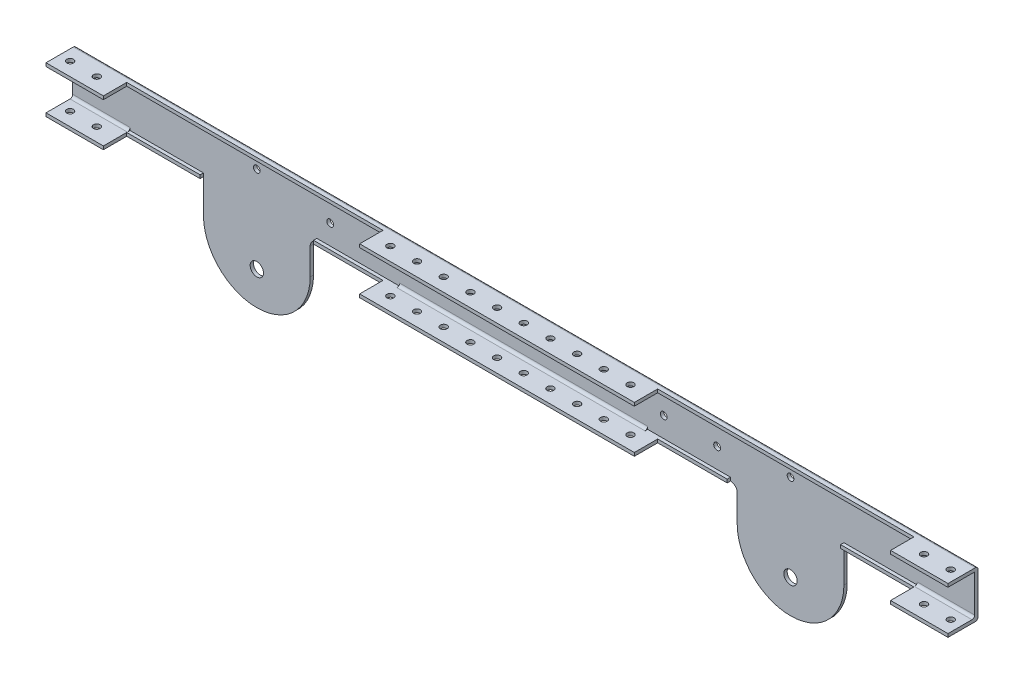
SolidWorks part; units mm, degrees
ref_plane "Front Plane" through (0, 0, 0) normal (0, 0, 1) x (1, 0, 0)
ref_plane "Top Plane" through (0, 0, 0) normal (0, 1, 0) x (1, 0, 0)
ref_plane "Right Plane" through (0, 0, 0) normal (1, 0, 0) x (0, 0, -1)
sketch "Sketch1" plane through (0, 0, 0) normal (0, 0, 1) x (1, 0, 0)
  line L0 (50.8, 0) -> (50.8, 25.4)
  line L1 (-50.8, 0) -> (-50.8, 76.2)
  line L2 (57.15, 31.75) -> (438.15, 31.75)
  line L3 (444.5, 25.4) -> (444.5, 0)
  line L4 (546.1, 0) -> (546.1, 76.2)
  line L5 (-50.8, 76.2) -> (546.1, 76.2)
  arc A0 (-50.8, 0) -> (50.8, 0) centre (0, 0) ccw
  arc A1 (50.8, 25.4) -> (57.15, 31.75) centre (57.15, 25.4) cw
  arc A2 (438.15, 31.75) -> (444.5, 25.4) centre (438.15, 25.4) cw
  arc A3 (444.5, 0) -> (546.1, 0) centre (495.3, 0) ccw
  circle A4 centre (0, 0) radius 6.35
  circle A5 centre (495.3, 0) radius 6.35
  dimension "D1" = 101.6
  dimension "D2" = 6.35
  dimension "D4" = 6.35
  dimension "D6" = 76.2
  dimension "D3" = 381
  dimension "D5" = 25.4
  dimension "D7" = 76.2
extrude "Boss-Extrude1" add sketch "Sketch1" along normal blind 3.175
sketch "Sketch2" plane through (0, 0, 3.175) normal (0, 0, 1) x (1, 0, 0)
  line L0 (-50.8, 76.2) -> (-50.8, 73.025)
  line L1 (-50.8, 76.2) -> (-50.8, 0) construction
  line L2 (546.1, 76.2) -> (-50.8, 76.2)
  line L3 (-50.8, 73.025) -> (546.1, 73.025)
  line L4 (546.1, 0) -> (546.1, 76.2) construction
  line L5 (546.1, 73.025) -> (546.1, 76.2)
  dimension "D1" = 3.175
extrude "Boss-Extrude2" add sketch "Sketch2" along normal blind 25.4
fillet "Fillet1" radius 2.54 2 edges at (247.65, 76.2, 0)
sketch "Sketch3" plane through (0, 76.2, 0) normal (0, 1, 0) x (1, 0, 0)
  line L0 (546.1, -28.575) -> (546.1, -2.54)
  circle A0 centre (527.05, -15.5575) radius 3.2639
  circle A1 centre (501.65, -15.5575) radius 3.2639
  circle A2 centre (476.25, -15.5575) radius 3.2639
  circle A3 centre (450.85, -15.5575) radius 3.2639
  circle A4 centre (425.45, -15.5575) radius 3.2639
  circle A5 centre (400.05, -15.5575) radius 3.2639
  circle A6 centre (374.65, -15.5575) radius 3.2639
  circle A7 centre (349.25, -15.5575) radius 3.2639
  circle A8 centre (323.85, -15.5575) radius 3.2639
  circle A9 centre (298.45, -15.5575) radius 3.2639
  circle A10 centre (273.05, -15.5575) radius 3.2639
  circle A11 centre (247.65, -15.5575) radius 3.2639
  circle A12 centre (222.25, -15.5575) radius 3.2639
  circle A13 centre (196.85, -15.5575) radius 3.2639
  circle A14 centre (171.45, -15.5575) radius 3.2639
  circle A15 centre (146.05, -15.5575) radius 3.2639
  circle A16 centre (120.65, -15.5575) radius 3.2639
  circle A17 centre (95.25, -15.5575) radius 3.2639
  circle A18 centre (69.85, -15.5575) radius 3.2639
  circle A19 centre (44.45, -15.5575) radius 3.2639
  circle A20 centre (19.05, -15.5575) radius 3.2639
  circle A21 centre (-6.35, -15.5575) radius 3.2639
  circle A22 centre (-31.75, -15.5575) radius 3.2639
  dimension "D1" = 19.05
  dimension "D2" = 23
extrude "Cut-Extrude1" cut sketch "Sketch3" against normal blind 25.4 contours A0 | A1 | A2 | A3 | A22 | A21 | A20 | A19 | A18 | A17 | A16 | A15 | A14 | A13 | A12 | A11 | A10 | A9 | A8 | A7 | A6 | A5 | A4 region at (527.05, 76.2, 15.5575) region at (501.65, 76.2, 15.5575) region at (476.25, 76.2, 15.5575) region at (450.85, 76.2, 15.5575) region at (425.45, 76.2, 15.5575) region at (400.05, 76.2, 15.5575) region at (374.65, 76.2, 15.5575) region at (349.25, 76.2, 15.5575) region at (323.85, 76.2, 15.5575) region at (298.45, 76.2, 15.5575) region at (273.05, 76.2, 15.5575) region at (247.65, 76.2, 15.5575) region at (222.25, 76.2, 15.5575) region at (196.85, 76.2, 15.5575) region at (171.45, 76.2, 15.5575) region at (146.05, 76.2, 15.5575) region at (120.65, 76.2, 15.5575) region at (95.25, 76.2, 15.5575) region at (69.85, 76.2, 15.5575) region at (44.45, 76.2, 15.5575) region at (19.05, 76.2, 15.5575) region at (-6.35, 76.2, 15.5575) region at (-31.75, 76.2, 15.5575)
sketch "Sketch5" plane through (0, 0, 0) normal (0, 0, -1) x (-1, 0, 0)
  line L0 (-444.5, 25.4) -> (-444.5, 0) construction
  circle A0 centre (-425.45, 53.975) radius 3.2639
  circle A1 centre (-374.65, 53.975) radius 3.2639
  circle A2 centre (-323.85, 53.975) radius 3.2639
  circle A3 centre (-273.05, 53.975) radius 3.2639
  circle A4 centre (-222.25, 53.975) radius 3.2639
  circle A5 centre (-171.45, 53.975) radius 3.2639
  circle A6 centre (-120.65, 53.975) radius 3.2639
  circle A7 centre (-69.85, 53.975) radius 3.2639
  dimension "D1" = 6.5278
  dimension "D2" = 19.05
  dimension "D3" = 8
extrude "Cut-Extrude2" cut sketch "Sketch5" against normal blind 25.4
sketch "Sketch6" plane through (0, 0, 3.175) normal (0, 0, 1) x (1, 0, 0)
  line L1 (-50.8, 76.2) -> (-82.55, 76.2)
  line L2 (-50.8, 76.2) -> (-50.8, 31.75)
  line L3 (-50.8, 31.75) -> (-82.55, 31.75)
  line L4 (-82.55, 76.2) -> (-82.55, 31.75)
  line L5 (546.1, 76.2) -> (577.85, 76.2)
  line L6 (546.1, 76.2) -> (546.1, 31.75)
  line L7 (546.1, 31.75) -> (577.85, 31.75)
  line L8 (577.85, 76.2) -> (577.85, 31.75)
  dimension "D1" = 31.75
  dimension "D2" = 31.75
extrude "Boss-Extrude3" add sketch "Sketch6" against normal blind 3.175
sketch "Sketch7" plane through (0, 0, 3.175) normal (0, 0, 1) x (1, 0, 0)
  line L1 (57.15, 31.75) -> (438.15, 31.75) construction
  line L2 (-50.8, 73.025) -> (-82.55, 73.025)
  line L3 (-50.8, 73.025) -> (-50.8, 76.2)
  line L4 (-50.8, 76.2) -> (-82.55, 76.2)
  line L5 (-82.55, 31.75) -> (-50.8, 31.75)
  line L6 (-82.55, 31.75) -> (-82.55, 34.925)
  line L7 (-82.55, 34.925) -> (-50.8, 34.925)
  line L8 (-50.8, 31.75) -> (-50.8, 34.925)
  line L9 (577.85, 31.75) -> (577.85, 76.2) construction
  line L10 (546.1, 76.2) -> (577.85, 76.2)
  line L11 (546.1, 76.2) -> (546.1, 73.025)
  line L12 (546.1, 73.025) -> (577.85, 73.025)
  line L13 (577.85, 76.2) -> (577.85, 73.025)
  line L14 (-82.55, 73.025) -> (-82.55, 76.2)
  line L15 (577.85, 31.75) -> (546.1, 31.75)
  line L16 (577.85, 31.75) -> (577.85, 34.925)
  line L17 (577.85, 34.925) -> (546.1, 34.925)
  line L18 (546.1, 31.75) -> (546.1, 34.925)
  line L19 (57.15, 31.75) -> (438.15, 31.75)
  line L20 (57.15, 31.75) -> (57.15, 34.925)
  line L21 (57.15, 34.925) -> (438.15, 34.925)
  line L22 (438.15, 31.75) -> (438.15, 34.925)
  arc A0 (57.15, 31.75) -> (50.8, 25.4) centre (57.15, 25.4) ccw construction
  dimension "D1" = 3.175
  dimension "D2" = 3.175
  dimension "D3" = 3.175
extrude "Boss-Extrude4" add sketch "Sketch7" along normal blind 25.4
fillet "Fillet2" radius 2.54 16 edges at (-50.8, 15.875, 0) (0, -50.8, 0) (50.8, 12.7, 0) (52.6599, 29.8901, 0) (546.1, 15.875, 0) (495.3, -50.8, 0) (444.5, 12.7, 0) (442.6401, 29.8901, 0) (-66.675, 34.925, 3.175) (-66.675, 31.75, 0) (247.65, 31.75, 0) (247.65, 34.925, 3.175) (561.975, 34.925, 3.175) (561.975, 31.75, 0) (561.975, 76.2, 0) (-66.675, 76.2, 0)
sketch "Sketch8" plane through (0, 76.2, 0) normal (0, 1, 0) x (1, 0, 0)
  circle A0 centre (-31.75, -15.5575) radius 3.2639 construction
  circle A1 centre (-31.75, -15.5575) radius 3.2639
  circle A2 centre (-57.15, -15.5575) radius 3.2639
  circle A3 centre (-31.75, -15.5575) radius 3.2639
  circle A4 centre (-6.35, -15.5575) radius 3.2639
  circle A5 centre (19.05, -15.5575) radius 3.2639
  circle A6 centre (44.45, -15.5575) radius 3.2639
  circle A7 centre (69.85, -15.5575) radius 3.2639
  circle A8 centre (95.25, -15.5575) radius 3.2639
  circle A9 centre (120.65, -15.5575) radius 3.2639
  circle A10 centre (146.05, -15.5575) radius 3.2639
  circle A11 centre (171.45, -15.5575) radius 3.2639
  circle A12 centre (196.85, -15.5575) radius 3.2639
  circle A13 centre (222.25, -15.5575) radius 3.2639
  circle A14 centre (247.65, -15.5575) radius 3.2639
  circle A15 centre (273.05, -15.5575) radius 3.2639
  circle A16 centre (298.45, -15.5575) radius 3.2639
  circle A17 centre (323.85, -15.5575) radius 3.2639
  circle A18 centre (349.25, -15.5575) radius 3.2639
  circle A19 centre (374.65, -15.5575) radius 3.2639
  circle A20 centre (400.05, -15.5575) radius 3.2639
  circle A21 centre (425.45, -15.5575) radius 3.2639
  circle A22 centre (450.85, -15.5575) radius 3.2639
  circle A23 centre (476.25, -15.5575) radius 3.2639
  circle A24 centre (501.65, -15.5575) radius 3.2639
  circle A25 centre (527.05, -15.5575) radius 3.2639
  circle A26 centre (-6.35, -15.5575) radius 3.2639
  circle A27 centre (19.05, -15.5575) radius 3.2639
  circle A28 centre (44.45, -15.5575) radius 3.2639
  circle A29 centre (69.85, -15.5575) radius 3.2639
  circle A30 centre (95.25, -15.5575) radius 3.2639
  circle A31 centre (120.65, -15.5575) radius 3.2639
  circle A32 centre (146.05, -15.5575) radius 3.2639
  circle A33 centre (171.45, -15.5575) radius 3.2639
  circle A34 centre (196.85, -15.5575) radius 3.2639
  circle A35 centre (222.25, -15.5575) radius 3.2639
  circle A36 centre (247.65, -15.5575) radius 3.2639
  circle A37 centre (273.05, -15.5575) radius 3.2639
  circle A38 centre (298.45, -15.5575) radius 3.2639
  circle A39 centre (323.85, -15.5575) radius 3.2639
  circle A40 centre (349.25, -15.5575) radius 3.2639
  circle A41 centre (374.65, -15.5575) radius 3.2639
  circle A42 centre (400.05, -15.5575) radius 3.2639
  circle A43 centre (425.45, -15.5575) radius 3.2639
  circle A44 centre (450.85, -15.5575) radius 3.2639
  circle A45 centre (476.25, -15.5575) radius 3.2639
  circle A46 centre (501.65, -15.5575) radius 3.2639
  circle A47 centre (527.05, -15.5575) radius 3.2639
  circle A48 centre (552.45, -15.5575) radius 3.2639
  circle M1 centre (425.45, -15.5575) radius 3.2639
  circle M2 centre (400.05, -15.5575) radius 3.2639
  circle M3 centre (374.65, -15.5575) radius 3.2639
  circle M4 centre (349.25, -15.5575) radius 3.2639
  circle M5 centre (323.85, -15.5575) radius 3.2639
  circle M6 centre (298.45, -15.5575) radius 3.2639
  circle M7 centre (273.05, -15.5575) radius 3.2639
  circle M8 centre (247.65, -15.5575) radius 3.2639
  circle M9 centre (222.25, -15.5575) radius 3.2639
  circle M10 centre (196.85, -15.5575) radius 3.2639
  circle M11 centre (171.45, -15.5575) radius 3.2639
  circle M12 centre (146.05, -15.5575) radius 3.2639
  circle M13 centre (120.65, -15.5575) radius 3.2639
  circle M14 centre (95.25, -15.5575) radius 3.2639
  circle M15 centre (69.85, -15.5575) radius 3.2639
  circle M16 centre (44.45, -15.5575) radius 3.2639
  circle M17 centre (19.05, -15.5575) radius 3.2639
  circle M18 centre (-6.35, -15.5575) radius 3.2639
  circle M19 centre (-31.75, -15.5575) radius 3.2639
  circle M20 centre (450.85, -15.5575) radius 3.2639
  circle M21 centre (476.25, -15.5575) radius 3.2639
  circle M22 centre (501.65, -15.5575) radius 3.2639
  circle M23 centre (527.05, -15.5575) radius 3.2639
  dimension "D1" = 2
  dimension "D2" = 24
extrude "Cut-Extrude3" cut sketch "Sketch8" against normal blind 177.8 contours A2 | M19 | M18 | M17 | M16 | M15 | M14 | M13 | M12 | M11 | M10 | M9 | M8 | M7 | M6 | M5 | M4 | M3 | M2 | M1 | M20 | M21 | A48 | M23 | M22 region at (-31.75, 76.2, 15.5575) region at (-57.15, 76.2, 15.5575) region at (-6.35, 76.2, 15.5575) region at (19.05, 76.2, 15.5575) region at (44.45, 76.2, 15.5575) region at (69.85, 76.2, 15.5575) region at (95.25, 76.2, 15.5575) region at (120.65, 76.2, 15.5575) region at (146.05, 76.2, 15.5575) region at (171.45, 76.2, 15.5575) region at (196.85, 76.2, 15.5575) region at (222.25, 76.2, 15.5575) region at (247.65, 76.2, 15.5575) region at (273.05, 76.2, 15.5575) region at (298.45, 76.2, 15.5575) region at (323.85, 76.2, 15.5575) region at (349.25, 76.2, 15.5575) region at (374.65, 76.2, 15.5575) region at (400.05, 76.2, 15.5575) region at (425.45, 76.2, 15.5575) region at (450.85, 76.2, 15.5575) region at (476.25, 76.2, 15.5575) region at (501.65, 76.2, 15.5575) region at (527.05, 76.2, 15.5575) region at (552.45, 76.2, 15.5575)
sketch "Sketch9" plane through (0, 76.2, 0) normal (0, 1, 0) x (1, 0, 0)
  line L0 (-82.55, -28.575) -> (298.45, -28.575)
  line L1 (577.85, -28.575) -> (-82.55, -28.575) construction
  line L3 (298.45, -28.575) -> (746.3929, -28.575)
  line L4 (298.45, -28.575) -> (298.45, 89.0041)
  line L5 (298.45, 89.0041) -> (746.3929, 89.0041)
  line L6 (746.3929, -28.575) -> (746.3929, 89.0041)
  circle M1 centre (552.45, -15.5575) radius 3.2639
  circle M3 centre (425.45, -15.5575) radius 3.2639
  circle M4 centre (400.05, -15.5575) radius 3.2639
  circle M5 centre (374.65, -15.5575) radius 3.2639
  circle M6 centre (349.25, -15.5575) radius 3.2639
  circle M7 centre (323.85, -15.5575) radius 3.2639
  circle M8 centre (298.45, -15.5575) radius 3.2639
  circle M22 centre (450.85, -15.5575) radius 3.2639
  circle M23 centre (476.25, -15.5575) radius 3.2639
  circle M24 centre (501.65, -15.5575) radius 3.2639
  circle M25 centre (527.05, -15.5575) radius 3.2639
  line M26 (577.85, -28.575) -> (577.85, -2.54)
  line M27 (577.85, -2.54) -> (546.1, -2.54)
  line M28 (546.1, -2.54) -> (-50.8, -2.54)
  line M31 (-82.55, -28.575) -> (577.85, -28.575)
extrude "Cut-Extrude5" cut sketch "Sketch9" against normal blind 432.308 contours L4 M31 M26 M27 M28 M8 M4 M6 M22 M24 M25 M23 M7 M5 M3 M1 | L3 L6 L5 L4 M28 M27 M26 region at (438.4843, 76.2, 15.5575) region at (535.9254, 76.2, -37.5492)
mirror "Mirror4" about plane through (298.45, -356.108, 0) normal (1, 0, 0) of bodies 110
sketch "Sketch10" plane through (-82.55, 0, 0) normal (-1, 0, 0) x (0, 0, 1)
  line L8 (0, 73.66) -> (0, 34.29)
  line L9 (2.54, 31.75) -> (28.575, 31.75)
  line L10 (28.575, 31.75) -> (28.575, 34.925)
  line L11 (28.575, 34.925) -> (5.715, 34.925)
  line L12 (3.175, 37.465) -> (3.175, 73.025)
  line L13 (3.175, 73.025) -> (28.575, 73.025)
  line L14 (28.575, 73.025) -> (28.575, 76.2)
  line L15 (28.575, 76.2) -> (2.54, 76.2)
  line L16 (0, 73.66) -> (0, 34.29)
  line L17 (2.54, 31.75) -> (28.575, 31.75)
  line L18 (28.575, 31.75) -> (28.575, 34.925)
  line L19 (28.575, 34.925) -> (5.715, 34.925)
  line L20 (3.175, 37.465) -> (3.175, 73.025)
  line L21 (3.175, 73.025) -> (28.575, 73.025)
  line L22 (28.575, 73.025) -> (28.575, 76.2)
  line L23 (28.575, 76.2) -> (2.54, 76.2)
  arc A3 (0, 34.29) -> (2.54, 31.75) centre (2.54, 34.29) ccw
  arc A4 (3.175, 37.465) -> (5.715, 34.925) centre (5.715, 37.465) ccw
  arc A5 (2.54, 76.2) -> (0, 73.66) centre (2.54, 73.66) ccw
  arc A6 (0, 34.29) -> (2.54, 31.75) centre (2.54, 34.29) ccw
  arc A7 (3.175, 37.465) -> (5.715, 34.925) centre (5.715, 37.465) ccw
  arc A8 (2.54, 76.2) -> (0, 73.66) centre (2.54, 73.66) ccw
  dimension "D1" = 0
extrude "Boss-Extrude6" add sketch "Sketch10" along normal blind 66.675
sketch "Sketch11" plane through (679.45, 0, 0) normal (1, 0, 0) x (0, 0, -1)
  line L8 (0, 34.29) -> (0, 73.66)
  line L9 (-2.54, 76.2) -> (-28.575, 76.2)
  line L10 (-28.575, 76.2) -> (-28.575, 73.025)
  line L11 (-28.575, 73.025) -> (-3.175, 73.025)
  line L12 (-3.175, 73.025) -> (-3.175, 37.465)
  line L13 (-5.715, 34.925) -> (-28.575, 34.925)
  line L14 (-28.575, 34.925) -> (-28.575, 31.75)
  line L15 (-28.575, 31.75) -> (-2.54, 31.75)
  line L16 (0, 34.29) -> (0, 73.66)
  line L17 (-2.54, 76.2) -> (-28.575, 76.2)
  line L18 (-28.575, 76.2) -> (-28.575, 73.025)
  line L19 (-28.575, 73.025) -> (-3.175, 73.025)
  line L20 (-3.175, 73.025) -> (-3.175, 37.465)
  line L21 (-5.715, 34.925) -> (-28.575, 34.925)
  line L22 (-28.575, 34.925) -> (-28.575, 31.75)
  line L23 (-28.575, 31.75) -> (-2.54, 31.75)
  arc A3 (0, 73.66) -> (-2.54, 76.2) centre (-2.54, 73.66) ccw
  arc A4 (-5.715, 34.925) -> (-3.175, 37.465) centre (-5.715, 37.465) ccw
  arc A5 (-2.54, 31.75) -> (0, 34.29) centre (-2.54, 34.29) ccw
  arc A6 (0, 73.66) -> (-2.54, 76.2) centre (-2.54, 73.66) ccw
  arc A7 (-5.715, 34.925) -> (-3.175, 37.465) centre (-5.715, 37.465) ccw
  arc A8 (-2.54, 31.75) -> (0, 34.29) centre (-2.54, 34.29) ccw
  dimension "D1" = 0
extrude "Boss-Extrude7" add sketch "Sketch11" along normal blind 66.675
sketch "Sketch12" plane through (0, 0, 3.175) normal (0, 0, 1) x (1, 0, 0)
  line L1 (114.3, 114.3) -> (-114.3, 114.3)
  line L2 (460.9211, 135.1062) -> (717.55, 135.1062)
  line L3 (460.9211, 135.1062) -> (460.9211, -117.6098)
  line L4 (482.6, 135.1062) -> (692.7253, 135.1062)
  line L5 (692.7253, 135.1062) -> (711.2, 135.1062)
  line L6 (460.9211, -117.6098) -> (717.55, -117.6098)
  line L7 (717.55, 135.1062) -> (717.55, -117.6098)
  line L8 (482.6, 135.1062) -> (460.9211, 135.1062)
  line L11 (460.9211, 135.1062) -> (460.9211, -59.2459)
  line L12 (711.2, 135.1062) -> (717.55, 135.1062)
  line L15 (717.55, 135.1062) -> (717.55, 3.7539)
  line L16 (114.3, 114.3) -> (135.9789, 114.3)
  line L17 (114.3, 0) -> (114.3, -15.4588)
  line L18 (114.3, -15.4588) -> (135.9789, -15.4588)
  line L19 (135.9789, 114.3) -> (135.9789, -15.4588)
  line L20 (-114.3, 114.3) -> (-120.65, 114.3)
  line L21 (-114.3, 0) -> (-114.3, -7.9863)
  line L22 (-114.3, -7.9863) -> (-120.65, -7.9863)
  line L23 (-120.65, 114.3) -> (-120.65, -7.9863)
  arc A0 (-114.3, 0) -> (114.3, 0) centre (0, 0) ccw
  circle M1 centre (0, 0) radius 6.35
  circle M5 centre (120.65, 53.975) radius 3.2639
  circle M6 centre (69.85, 53.975) radius 3.2639
  line M7 (57.15, 37.465) -> (539.75, 37.465)
  line M8 (539.75, 37.465) -> (539.75, 31.75)
  arc M9 (539.75, 31.75) -> (546.1, 25.4) centre (539.75, 25.4) cw
  line M10 (546.1, 25.4) -> (546.1, 0)
  arc M11 (546.1, 0) -> (647.7, 0) centre (596.9, 0) ccw
  line M12 (647.7, 0) -> (647.7, 31.75)
  line M13 (647.7, 31.75) -> (647.7, 37.465)
  line M14 (647.7, 37.465) -> (746.125, 37.465)
  line M16 (746.125, 73.025) -> (647.7, 73.025)
  line M17 (647.7, 73.025) -> (647.7, 70.485)
  line M18 (647.7, 70.485) -> (-50.8, 70.485)
  line M19 (-50.8, 70.485) -> (-50.8, 73.025)
  line M20 (-50.8, 73.025) -> (-149.225, 73.025)
  line M22 (-149.225, 37.465) -> (-50.8, 37.465)
  line M23 (-50.8, 37.465) -> (-50.8, 31.75)
  line M24 (-50.8, 31.75) -> (-50.8, 0)
  arc M25 (-50.8, 0) -> (50.8, 0) centre (0, 0) ccw
  line M26 (50.8, 0) -> (50.8, 25.4)
  arc M27 (50.8, 25.4) -> (57.15, 31.75) centre (57.15, 25.4) cw
  line M28 (57.15, 31.75) -> (57.15, 37.465)
  circle M29 centre (596.9, 0) radius 6.35
  circle M33 centre (476.25, 53.975) radius 3.2639
  circle M34 centre (527.05, 53.975) radius 3.2639
  dimension "D1" = 13.335
  dimension "D2" = 6.35
  dimension "D3" = 13.335
  dimension "D4" = 6.35
extrude "Cut-Extrude8" cut sketch "Sketch12" along normal blind 66.675 contours L7 L3 L6 M14 M13 M12 M11 M10 M9 M8 M7 | L7 L3 M16 M17 M18 M7 M8 M9 M10 M11 M12 M13 M14 M34 M33 M29 | L7 L2 L3 M18 M17 M16 | L21 A0 L17 L18 L19 L23 L22 M7 M28 M27 M26 M25 M24 M23 M22 | L23 L19 M20 M22 M23 M24 M25 M26 M27 M28 M7 M18 M19 M6 M5 M1 | L20 L23 L19 L16 L1 M20 M19 M18 region at (9.1616, 92.7234, 3.175) region at (2.7974, 27.6189, 3.175) region at (132.9974, 11.0031, 3.175) region at (594.1026, 27.6189, 3.175) region at (588.2256, 103.1313, 3.175) region at (500.3355, 34.4666, 3.175)
sketch "Sketch13" plane through (0, 76.2, 0) normal (0, 1, 0) x (1, 0, 0)
  circle A0 centre (146.05, -15.5575) radius 3.2639 construction
  circle A1 centre (146.05, -15.5575) radius 3.2639
sketch "Sketch14" plane through (746.125, 0, 0) normal (1, 0, 0) x (0, 0, -1)
  line L8 (0, 34.29) -> (0, 73.66)
  line L9 (-2.54, 76.2) -> (-28.575, 76.2)
  line L10 (-28.575, 76.2) -> (-28.575, 73.025)
  line L11 (-28.575, 73.025) -> (-3.175, 73.025)
  line L12 (-3.175, 73.025) -> (-3.175, 37.465)
  line L13 (-5.715, 34.925) -> (-28.575, 34.925)
  line L14 (-28.575, 34.925) -> (-28.575, 31.75)
  line L15 (-28.575, 31.75) -> (-2.54, 31.75)
  line L16 (0, 34.29) -> (0, 73.66)
  line L17 (-2.54, 76.2) -> (-28.575, 76.2)
  line L18 (-28.575, 76.2) -> (-28.575, 73.025)
  line L19 (-28.575, 73.025) -> (-3.175, 73.025)
  line L20 (-3.175, 73.025) -> (-3.175, 37.465)
  line L21 (-5.715, 34.925) -> (-28.575, 34.925)
  line L22 (-28.575, 34.925) -> (-28.575, 31.75)
  line L23 (-28.575, 31.75) -> (-2.54, 31.75)
  arc A3 (-2.54, 31.75) -> (0, 34.29) centre (-2.54, 34.29) ccw
  arc A4 (0, 73.66) -> (-2.54, 76.2) centre (-2.54, 73.66) ccw
  arc A5 (-5.715, 34.925) -> (-3.175, 37.465) centre (-5.715, 37.465) ccw
  arc A6 (-2.54, 31.75) -> (0, 34.29) centre (-2.54, 34.29) ccw
  arc A7 (0, 73.66) -> (-2.54, 76.2) centre (-2.54, 73.66) ccw
  arc A8 (-5.715, 34.925) -> (-3.175, 37.465) centre (-5.715, 37.465) ccw
  dimension "D1" = 0
extrude "Boss-Extrude8" add sketch "Sketch14" along normal blind 19.05
sketch "Sketch15" plane through (-149.225, 0, 0) normal (-1, 0, 0) x (0, 0, 1)
  line L8 (0, 73.66) -> (0, 34.29)
  line L9 (2.54, 31.75) -> (28.575, 31.75)
  line L10 (28.575, 31.75) -> (28.575, 34.925)
  line L11 (28.575, 34.925) -> (5.715, 34.925)
  line L12 (3.175, 37.465) -> (3.175, 73.025)
  line L13 (3.175, 73.025) -> (28.575, 73.025)
  line L14 (28.575, 73.025) -> (28.575, 76.2)
  line L15 (28.575, 76.2) -> (2.54, 76.2)
  line L16 (0, 73.66) -> (0, 34.29)
  line L17 (2.54, 31.75) -> (28.575, 31.75)
  line L18 (28.575, 31.75) -> (28.575, 34.925)
  line L19 (28.575, 34.925) -> (5.715, 34.925)
  line L20 (3.175, 37.465) -> (3.175, 73.025)
  line L21 (3.175, 73.025) -> (28.575, 73.025)
  line L22 (28.575, 73.025) -> (28.575, 76.2)
  line L23 (28.575, 76.2) -> (2.54, 76.2)
  arc A3 (2.54, 76.2) -> (0, 73.66) centre (2.54, 73.66) ccw
  arc A4 (0, 34.29) -> (2.54, 31.75) centre (2.54, 34.29) ccw
  arc A5 (3.175, 37.465) -> (5.715, 34.925) centre (5.715, 37.465) ccw
  arc A6 (2.54, 76.2) -> (0, 73.66) centre (2.54, 73.66) ccw
  arc A7 (0, 34.29) -> (2.54, 31.75) centre (2.54, 34.29) ccw
  arc A8 (3.175, 37.465) -> (5.715, 34.925) centre (5.715, 37.465) ccw
  dimension "D1" = 0
extrude "Boss-Extrude9" add sketch "Sketch15" along normal blind 19.05
sketch "Sketch16" plane through (0, 76.2, 0) normal (0, 1, 0) x (1, 0, 0)
  circle A0 centre (146.05, -15.5575) radius 3.2639 construction
  circle A1 centre (146.05, -15.5575) radius 3.2639
  circle A2 centre (171.45, -15.5575) radius 3.2639
  circle A3 centre (196.85, -15.5575) radius 3.2639
  circle A4 centre (222.25, -15.5575) radius 3.2639
  circle A5 centre (247.65, -15.5575) radius 3.2639
  circle A6 centre (273.05, -15.5575) radius 3.2639
  circle A7 centre (298.45, -15.5575) radius 3.2639
  circle A8 centre (323.85, -15.5575) radius 3.2639
  circle A9 centre (349.25, -15.5575) radius 3.2639
  circle A10 centre (374.65, -15.5575) radius 3.2639
  circle A11 centre (400.05, -15.5575) radius 3.2639
  circle A12 centre (425.45, -15.5575) radius 3.2639
  circle A13 centre (450.85, -15.5575) radius 3.2639
  circle A14 centre (476.25, -15.5575) radius 3.2639
  circle A15 centre (501.65, -15.5575) radius 3.2639
  circle A16 centre (527.05, -15.5575) radius 3.2639
  circle A17 centre (552.45, -15.5575) radius 3.2639
  circle A18 centre (577.85, -15.5575) radius 3.2639
  circle A19 centre (603.25, -15.5575) radius 3.2639
  circle A20 centre (628.65, -15.5575) radius 3.2639
  circle A21 centre (654.05, -15.5575) radius 3.2639
  circle A22 centre (679.45, -15.5575) radius 3.2639
  circle A23 centre (704.85, -15.5575) radius 3.2639
  circle A24 centre (730.25, -15.5575) radius 3.2639
  circle A25 centre (755.65, -15.5575) radius 3.2639
  circle A26 centre (146.05, -15.5575) radius 3.2639
  circle A27 centre (171.45, -15.5575) radius 3.2639
  circle A28 centre (196.85, -15.5575) radius 3.2639
  circle A29 centre (222.25, -15.5575) radius 3.2639
  circle A30 centre (247.65, -15.5575) radius 3.2639
  circle A31 centre (273.05, -15.5575) radius 3.2639
  circle A32 centre (298.45, -15.5575) radius 3.2639
  circle A33 centre (323.85, -15.5575) radius 3.2639
  circle A34 centre (349.25, -15.5575) radius 3.2639
  circle A35 centre (374.65, -15.5575) radius 3.2639
  circle A36 centre (400.05, -15.5575) radius 3.2639
  circle A37 centre (425.45, -15.5575) radius 3.2639
  circle A38 centre (450.85, -15.5575) radius 3.2639
  circle A39 centre (476.25, -15.5575) radius 3.2639
  circle A40 centre (501.65, -15.5575) radius 3.2639
  circle A41 centre (527.05, -15.5575) radius 3.2639
  circle A42 centre (552.45, -15.5575) radius 3.2639
  circle A43 centre (577.85, -15.5575) radius 3.2639
  circle A44 centre (603.25, -15.5575) radius 3.2639
  circle A45 centre (628.65, -15.5575) radius 3.2639
  circle A46 centre (654.05, -15.5575) radius 3.2639
  circle A47 centre (679.45, -15.5575) radius 3.2639
  circle A48 centre (704.85, -15.5575) radius 3.2639
  circle A49 centre (730.25, -15.5575) radius 3.2639
  circle A50 centre (120.65, -15.5575) radius 3.2639
  circle A51 centre (146.05, -15.5575) radius 3.2639
  circle A52 centre (171.45, -15.5575) radius 3.2639
  circle A53 centre (196.85, -15.5575) radius 3.2639
  circle A54 centre (222.25, -15.5575) radius 3.2639
  circle A55 centre (247.65, -15.5575) radius 3.2639
  circle A56 centre (273.05, -15.5575) radius 3.2639
  circle A57 centre (298.45, -15.5575) radius 3.2639
  circle A58 centre (323.85, -15.5575) radius 3.2639
  circle A59 centre (349.25, -15.5575) radius 3.2639
  circle A60 centre (374.65, -15.5575) radius 3.2639
  circle A61 centre (400.05, -15.5575) radius 3.2639
  circle A62 centre (425.45, -15.5575) radius 3.2639
  circle A63 centre (450.85, -15.5575) radius 3.2639
  circle A64 centre (476.25, -15.5575) radius 3.2639
  circle A65 centre (501.65, -15.5575) radius 3.2639
  circle A66 centre (527.05, -15.5575) radius 3.2639
  circle A67 centre (552.45, -15.5575) radius 3.2639
  circle A68 centre (577.85, -15.5575) radius 3.2639
  circle A69 centre (603.25, -15.5575) radius 3.2639
  circle A70 centre (628.65, -15.5575) radius 3.2639
  circle A71 centre (654.05, -15.5575) radius 3.2639
  circle A72 centre (679.45, -15.5575) radius 3.2639
  circle A73 centre (704.85, -15.5575) radius 3.2639
  circle A74 centre (95.25, -15.5575) radius 3.2639
  circle A75 centre (120.65, -15.5575) radius 3.2639
  circle A76 centre (146.05, -15.5575) radius 3.2639
  circle A77 centre (171.45, -15.5575) radius 3.2639
  circle A78 centre (196.85, -15.5575) radius 3.2639
  circle A79 centre (222.25, -15.5575) radius 3.2639
  circle A80 centre (247.65, -15.5575) radius 3.2639
  circle A81 centre (273.05, -15.5575) radius 3.2639
  circle A82 centre (298.45, -15.5575) radius 3.2639
  circle A83 centre (323.85, -15.5575) radius 3.2639
  circle A84 centre (349.25, -15.5575) radius 3.2639
  circle A85 centre (374.65, -15.5575) radius 3.2639
  circle A86 centre (400.05, -15.5575) radius 3.2639
  circle A87 centre (425.45, -15.5575) radius 3.2639
  circle A88 centre (450.85, -15.5575) radius 3.2639
  circle A89 centre (476.25, -15.5575) radius 3.2639
  circle A90 centre (501.65, -15.5575) radius 3.2639
  circle A91 centre (527.05, -15.5575) radius 3.2639
  circle A92 centre (552.45, -15.5575) radius 3.2639
  circle A93 centre (577.85, -15.5575) radius 3.2639
  circle A94 centre (603.25, -15.5575) radius 3.2639
  circle A95 centre (628.65, -15.5575) radius 3.2639
  circle A96 centre (654.05, -15.5575) radius 3.2639
  circle A97 centre (679.45, -15.5575) radius 3.2639
  circle A98 centre (69.85, -15.5575) radius 3.2639
  circle A99 centre (95.25, -15.5575) radius 3.2639
  circle A100 centre (120.65, -15.5575) radius 3.2639
  circle A101 centre (146.05, -15.5575) radius 3.2639
  circle A102 centre (171.45, -15.5575) radius 3.2639
  circle A103 centre (196.85, -15.5575) radius 3.2639
  circle A104 centre (222.25, -15.5575) radius 3.2639
  circle A105 centre (247.65, -15.5575) radius 3.2639
  circle A106 centre (273.05, -15.5575) radius 3.2639
  circle A107 centre (298.45, -15.5575) radius 3.2639
  circle A108 centre (323.85, -15.5575) radius 3.2639
  circle A109 centre (349.25, -15.5575) radius 3.2639
  circle A110 centre (374.65, -15.5575) radius 3.2639
  circle A111 centre (400.05, -15.5575) radius 3.2639
  circle A112 centre (425.45, -15.5575) radius 3.2639
  circle A113 centre (450.85, -15.5575) radius 3.2639
  circle A114 centre (476.25, -15.5575) radius 3.2639
  circle A115 centre (501.65, -15.5575) radius 3.2639
  circle A116 centre (527.05, -15.5575) radius 3.2639
  circle A117 centre (552.45, -15.5575) radius 3.2639
  circle A118 centre (577.85, -15.5575) radius 3.2639
  circle A119 centre (603.25, -15.5575) radius 3.2639
  circle A120 centre (628.65, -15.5575) radius 3.2639
  circle A121 centre (654.05, -15.5575) radius 3.2639
  circle A122 centre (44.45, -15.5575) radius 3.2639
  circle A123 centre (69.85, -15.5575) radius 3.2639
  circle A124 centre (95.25, -15.5575) radius 3.2639
  circle A125 centre (120.65, -15.5575) radius 3.2639
  circle A126 centre (146.05, -15.5575) radius 3.2639
  circle A127 centre (171.45, -15.5575) radius 3.2639
  circle A128 centre (196.85, -15.5575) radius 3.2639
  circle A129 centre (222.25, -15.5575) radius 3.2639
  circle A130 centre (247.65, -15.5575) radius 3.2639
  circle A131 centre (273.05, -15.5575) radius 3.2639
  circle A132 centre (298.45, -15.5575) radius 3.2639
  circle A133 centre (323.85, -15.5575) radius 3.2639
  circle A134 centre (349.25, -15.5575) radius 3.2639
  circle A135 centre (374.65, -15.5575) radius 3.2639
  circle A136 centre (400.05, -15.5575) radius 3.2639
  circle A137 centre (425.45, -15.5575) radius 3.2639
  circle A138 centre (450.85, -15.5575) radius 3.2639
  circle A139 centre (476.25, -15.5575) radius 3.2639
  circle A140 centre (501.65, -15.5575) radius 3.2639
  circle A141 centre (527.05, -15.5575) radius 3.2639
  circle A142 centre (552.45, -15.5575) radius 3.2639
  circle A143 centre (577.85, -15.5575) radius 3.2639
  circle A144 centre (603.25, -15.5575) radius 3.2639
  circle A145 centre (628.65, -15.5575) radius 3.2639
  circle A146 centre (19.05, -15.5575) radius 3.2639
  circle A147 centre (44.45, -15.5575) radius 3.2639
  circle A148 centre (69.85, -15.5575) radius 3.2639
  circle A149 centre (95.25, -15.5575) radius 3.2639
  circle A150 centre (120.65, -15.5575) radius 3.2639
  circle A151 centre (146.05, -15.5575) radius 3.2639
  circle A152 centre (171.45, -15.5575) radius 3.2639
  circle A153 centre (196.85, -15.5575) radius 3.2639
  circle A154 centre (222.25, -15.5575) radius 3.2639
  circle A155 centre (247.65, -15.5575) radius 3.2639
  circle A156 centre (273.05, -15.5575) radius 3.2639
  circle A157 centre (298.45, -15.5575) radius 3.2639
  circle A158 centre (323.85, -15.5575) radius 3.2639
  circle A159 centre (349.25, -15.5575) radius 3.2639
  circle A160 centre (374.65, -15.5575) radius 3.2639
  circle A161 centre (400.05, -15.5575) radius 3.2639
  circle A162 centre (425.45, -15.5575) radius 3.2639
  circle A163 centre (450.85, -15.5575) radius 3.2639
  circle A164 centre (476.25, -15.5575) radius 3.2639
  circle A165 centre (501.65, -15.5575) radius 3.2639
  circle A166 centre (527.05, -15.5575) radius 3.2639
  circle A167 centre (552.45, -15.5575) radius 3.2639
  circle A168 centre (577.85, -15.5575) radius 3.2639
  circle A169 centre (603.25, -15.5575) radius 3.2639
  circle A170 centre (-6.35, -15.5575) radius 3.2639
  circle A171 centre (19.05, -15.5575) radius 3.2639
  circle A172 centre (44.45, -15.5575) radius 3.2639
  circle A173 centre (69.85, -15.5575) radius 3.2639
  circle A174 centre (95.25, -15.5575) radius 3.2639
  circle A175 centre (120.65, -15.5575) radius 3.2639
  circle A176 centre (146.05, -15.5575) radius 3.2639
  circle A177 centre (171.45, -15.5575) radius 3.2639
  circle A178 centre (196.85, -15.5575) radius 3.2639
  circle A179 centre (222.25, -15.5575) radius 3.2639
  circle A180 centre (247.65, -15.5575) radius 3.2639
  circle A181 centre (273.05, -15.5575) radius 3.2639
  circle A182 centre (298.45, -15.5575) radius 3.2639
  circle A183 centre (323.85, -15.5575) radius 3.2639
  circle A184 centre (349.25, -15.5575) radius 3.2639
  circle A185 centre (374.65, -15.5575) radius 3.2639
  circle A186 centre (400.05, -15.5575) radius 3.2639
  circle A187 centre (425.45, -15.5575) radius 3.2639
  circle A188 centre (450.85, -15.5575) radius 3.2639
  circle A189 centre (476.25, -15.5575) radius 3.2639
  circle A190 centre (501.65, -15.5575) radius 3.2639
  circle A191 centre (527.05, -15.5575) radius 3.2639
  circle A192 centre (552.45, -15.5575) radius 3.2639
  circle A193 centre (577.85, -15.5575) radius 3.2639
  circle A194 centre (-31.75, -15.5575) radius 3.2639
  circle A195 centre (-6.35, -15.5575) radius 3.2639
  circle A196 centre (19.05, -15.5575) radius 3.2639
  circle A197 centre (44.45, -15.5575) radius 3.2639
  circle A198 centre (69.85, -15.5575) radius 3.2639
  circle A199 centre (95.25, -15.5575) radius 3.2639
  circle A200 centre (120.65, -15.5575) radius 3.2639
  circle A201 centre (146.05, -15.5575) radius 3.2639
  circle A202 centre (171.45, -15.5575) radius 3.2639
  circle A203 centre (196.85, -15.5575) radius 3.2639
  circle A204 centre (222.25, -15.5575) radius 3.2639
  circle A205 centre (247.65, -15.5575) radius 3.2639
  circle A206 centre (273.05, -15.5575) radius 3.2639
  circle A207 centre (298.45, -15.5575) radius 3.2639
  circle A208 centre (323.85, -15.5575) radius 3.2639
  circle A209 centre (349.25, -15.5575) radius 3.2639
  circle A210 centre (374.65, -15.5575) radius 3.2639
  circle A211 centre (400.05, -15.5575) radius 3.2639
  circle A212 centre (425.45, -15.5575) radius 3.2639
  circle A213 centre (450.85, -15.5575) radius 3.2639
  circle A214 centre (476.25, -15.5575) radius 3.2639
  circle A215 centre (501.65, -15.5575) radius 3.2639
  circle A216 centre (527.05, -15.5575) radius 3.2639
  circle A217 centre (552.45, -15.5575) radius 3.2639
  circle A218 centre (-57.15, -15.5575) radius 3.2639
  circle A219 centre (-31.75, -15.5575) radius 3.2639
  circle A220 centre (-6.35, -15.5575) radius 3.2639
  circle A221 centre (19.05, -15.5575) radius 3.2639
  circle A222 centre (44.45, -15.5575) radius 3.2639
  circle A223 centre (69.85, -15.5575) radius 3.2639
  circle A224 centre (95.25, -15.5575) radius 3.2639
  circle A225 centre (120.65, -15.5575) radius 3.2639
  circle A226 centre (146.05, -15.5575) radius 3.2639
  circle A227 centre (171.45, -15.5575) radius 3.2639
  circle A228 centre (196.85, -15.5575) radius 3.2639
  circle A229 centre (222.25, -15.5575) radius 3.2639
  circle A230 centre (247.65, -15.5575) radius 3.2639
  circle A231 centre (273.05, -15.5575) radius 3.2639
  circle A232 centre (298.45, -15.5575) radius 3.2639
  circle A233 centre (323.85, -15.5575) radius 3.2639
  circle A234 centre (349.25, -15.5575) radius 3.2639
  circle A235 centre (374.65, -15.5575) radius 3.2639
  circle A236 centre (400.05, -15.5575) radius 3.2639
  circle A237 centre (425.45, -15.5575) radius 3.2639
  circle A238 centre (450.85, -15.5575) radius 3.2639
  circle A239 centre (476.25, -15.5575) radius 3.2639
  circle A240 centre (501.65, -15.5575) radius 3.2639
  circle A241 centre (527.05, -15.5575) radius 3.2639
  circle A242 centre (-82.55, -15.5575) radius 3.2639
  circle A243 centre (-57.15, -15.5575) radius 3.2639
  circle A244 centre (-31.75, -15.5575) radius 3.2639
  circle A245 centre (-6.35, -15.5575) radius 3.2639
  circle A246 centre (19.05, -15.5575) radius 3.2639
  circle A247 centre (44.45, -15.5575) radius 3.2639
  circle A248 centre (69.85, -15.5575) radius 3.2639
  circle A249 centre (95.25, -15.5575) radius 3.2639
  circle A250 centre (120.65, -15.5575) radius 3.2639
  circle A251 centre (146.05, -15.5575) radius 3.2639
  circle A252 centre (171.45, -15.5575) radius 3.2639
  circle A253 centre (196.85, -15.5575) radius 3.2639
  circle A254 centre (222.25, -15.5575) radius 3.2639
  circle A255 centre (247.65, -15.5575) radius 3.2639
  circle A256 centre (273.05, -15.5575) radius 3.2639
  circle A257 centre (298.45, -15.5575) radius 3.2639
  circle A258 centre (323.85, -15.5575) radius 3.2639
  circle A259 centre (349.25, -15.5575) radius 3.2639
  circle A260 centre (374.65, -15.5575) radius 3.2639
  circle A261 centre (400.05, -15.5575) radius 3.2639
  circle A262 centre (425.45, -15.5575) radius 3.2639
  circle A263 centre (450.85, -15.5575) radius 3.2639
  circle A264 centre (476.25, -15.5575) radius 3.2639
  circle A265 centre (501.65, -15.5575) radius 3.2639
  circle A266 centre (-107.95, -15.5575) radius 3.2639
  circle A267 centre (-82.55, -15.5575) radius 3.2639
  circle A268 centre (-57.15, -15.5575) radius 3.2639
  circle A269 centre (-31.75, -15.5575) radius 3.2639
  circle A270 centre (-6.35, -15.5575) radius 3.2639
  circle A271 centre (19.05, -15.5575) radius 3.2639
  circle A272 centre (44.45, -15.5575) radius 3.2639
  circle A273 centre (69.85, -15.5575) radius 3.2639
  circle A274 centre (95.25, -15.5575) radius 3.2639
  circle A275 centre (120.65, -15.5575) radius 3.2639
  circle A276 centre (146.05, -15.5575) radius 3.2639
  circle A277 centre (171.45, -15.5575) radius 3.2639
  circle A278 centre (196.85, -15.5575) radius 3.2639
  circle A279 centre (222.25, -15.5575) radius 3.2639
  circle A280 centre (247.65, -15.5575) radius 3.2639
  circle A281 centre (273.05, -15.5575) radius 3.2639
  circle A282 centre (298.45, -15.5575) radius 3.2639
  circle A283 centre (323.85, -15.5575) radius 3.2639
  circle A284 centre (349.25, -15.5575) radius 3.2639
  circle A285 centre (374.65, -15.5575) radius 3.2639
  circle A286 centre (400.05, -15.5575) radius 3.2639
  circle A287 centre (425.45, -15.5575) radius 3.2639
  circle A288 centre (450.85, -15.5575) radius 3.2639
  circle A289 centre (476.25, -15.5575) radius 3.2639
  circle A290 centre (-133.35, -15.5575) radius 3.2639
  circle A291 centre (-107.95, -15.5575) radius 3.2639
  circle A292 centre (-82.55, -15.5575) radius 3.2639
  circle A293 centre (-57.15, -15.5575) radius 3.2639
  circle A294 centre (-31.75, -15.5575) radius 3.2639
  circle A295 centre (-6.35, -15.5575) radius 3.2639
  circle A296 centre (19.05, -15.5575) radius 3.2639
  circle A297 centre (44.45, -15.5575) radius 3.2639
  circle A298 centre (69.85, -15.5575) radius 3.2639
  circle A299 centre (95.25, -15.5575) radius 3.2639
  circle A300 centre (120.65, -15.5575) radius 3.2639
  circle A301 centre (146.05, -15.5575) radius 3.2639
  circle A302 centre (171.45, -15.5575) radius 3.2639
  circle A303 centre (196.85, -15.5575) radius 3.2639
  circle A304 centre (222.25, -15.5575) radius 3.2639
  circle A305 centre (247.65, -15.5575) radius 3.2639
  circle A306 centre (273.05, -15.5575) radius 3.2639
  circle A307 centre (298.45, -15.5575) radius 3.2639
  circle A308 centre (323.85, -15.5575) radius 3.2639
  circle A309 centre (349.25, -15.5575) radius 3.2639
  circle A310 centre (374.65, -15.5575) radius 3.2639
  circle A311 centre (400.05, -15.5575) radius 3.2639
  circle A312 centre (425.45, -15.5575) radius 3.2639
  circle A313 centre (450.85, -15.5575) radius 3.2639
  circle A314 centre (120.65, -15.5575) radius 3.2639
  circle A315 centre (95.25, -15.5575) radius 3.2639
  circle A316 centre (69.85, -15.5575) radius 3.2639
  circle A317 centre (44.45, -15.5575) radius 3.2639
  circle A318 centre (19.05, -15.5575) radius 3.2639
  circle A319 centre (-6.35, -15.5575) radius 3.2639
  circle A320 centre (-31.75, -15.5575) radius 3.2639
  circle A321 centre (-57.15, -15.5575) radius 3.2639
  circle A322 centre (-82.55, -15.5575) radius 3.2639
  circle A323 centre (-107.95, -15.5575) radius 3.2639
  circle A324 centre (-133.35, -15.5575) radius 3.2639
  circle A325 centre (-158.75, -15.5575) radius 3.2639
  dimension "D1" = 25
  dimension "D2" = 13
extrude "Cut-Extrude9" cut sketch "Sketch16" against normal blind 133.096
sketch "Sketch17" plane through (0, 0, 0) normal (0, 0, -1) x (-1, 0, 0)
  line L0 (-647.7, 76.2) -> (50.8, 76.2) construction
  circle A0 centre (0, 63.5) radius 3.175
  circle A1 centre (-596.9, 63.5) radius 3.175
  dimension "D1" = 12.7
extrude "Cut-Extrude11" cut sketch "Sketch17" against normal blind 5.08
sketch "Sketch18" plane through (0, 0, 3.175) normal (0, 0, 1) x (1, 0, 0)
  line L1 (-120.65, 73.025) -> (135.9789, 73.025)
  line L2 (-120.65, 73.025) -> (-120.65, 76.2)
  line L3 (-120.65, 76.2) -> (135.9789, 76.2)
  line L4 (135.9789, 73.025) -> (135.9789, 76.2)
  line L5 (460.9211, 76.2) -> (717.55, 76.2)
  line L6 (460.9211, 76.2) -> (460.9211, 73.025)
  line L7 (460.9211, 73.025) -> (717.55, 73.025)
  line L8 (717.55, 76.2) -> (717.55, 73.025)
  line L9 (717.55, 31.75) -> (-120.65, 31.75)
  line L10 (717.55, 31.75) -> (717.55, 34.925)
  line L11 (717.55, 34.925) -> (-120.65, 34.925)
  line L12 (-120.65, 31.75) -> (-120.65, 34.925)
extrude "Boss-Extrude10" add sketch "Sketch18" along normal blind 3.175
sketch "Sketch19" plane through (0, 0, 3.175) normal (0, 0, 1) x (1, 0, 0)
  line L0 (717.55, 34.925) -> (460.9211, 34.925) construction
  line L1 (-50.8, 31.75) -> (57.1504, 31.75)
  line L2 (-50.8, 31.75) -> (-50.8, 38.1387)
  line L3 (-50.8, 38.1387) -> (57.1504, 38.1387)
  line L4 (57.1504, 31.75) -> (57.1504, 38.1387)
  line L5 (647.7, 34.925) -> (539.75, 34.925)
  line L6 (647.7, 34.925) -> (647.7, 31.75)
  line L7 (647.7, 31.75) -> (539.75, 31.75)
  line L8 (539.75, 34.925) -> (539.75, 31.75)
extrude "Cut-Extrude12" cut sketch "Sketch19" along normal blind 3.175
sketch "Sketch20" plane through (0, 0, 0) normal (0, 0, -1) x (-1, 0, 0)
  line L0 (-342.9, 184.1305) -> (-342.9, -54.1947)
  line L2 (-342.9, 184.1305) -> (212.3723, 184.1305)
  line L3 (-342.9, 184.1305) -> (-342.9, -60.2979)
  line L4 (-342.9, -60.2979) -> (212.3723, -60.2979)
  line L5 (212.3723, 184.1305) -> (212.3723, -60.2979)
  circle A0 centre (-596.9, 0) radius 6.35 construction
  circle M3 centre (0, 63.5) radius 3.175
  circle M4 centre (0, 0) radius 6.35
  circle M5 centre (-273.05, 53.975) radius 3.2639
  circle M6 centre (-222.25, 53.975) radius 3.2639
  circle M7 centre (-171.45, 53.975) radius 3.2639
  circle M8 centre (-120.65, 53.975) radius 3.2639
  circle M9 centre (-69.85, 53.975) radius 3.2639
  line M10 (50.8, 73.66) -> (-647.7, 73.66)
  line M18 (-539.75, 34.29) -> (-57.15, 34.29)
  arc M19 (-57.15, 34.29) -> (-48.26, 25.4) centre (-57.15, 25.4) cw
  line M20 (-48.26, 25.4) -> (-48.26, 0)
  arc M21 (-48.26, 0) -> (48.26, 0) centre (0, 0) ccw
  line M22 (48.26, 0) -> (48.26, 34.29)
  line M23 (48.26, 34.29) -> (168.275, 34.29)
  line M24 (168.275, 34.29) -> (168.275, 73.66)
  line M25 (168.275, 73.66) -> (50.8, 73.66)
  circle M27 centre (-323.85, 53.975) radius 3.2639
  dimension "D1" = 254
extrude "Cut-Extrude13" cut sketch "Sketch20" against normal blind 277.622 contours L0 M10 M18 M19 M20 M21 M22 M23 M24 M25 M4 M6 M8 M27 M9 M7 M5 M3 | L5 L2 L0 L3 L4 M10 M25 M24 M23 M22 M21 M20 M19 M18 region at (65.2639, 178.0636, 0) region at (64.2403, 39.4662, 0)
sketch "Sketch21" plane through (0, 0, 3.175) normal (0, 0, 1) x (1, 0, 0)
  line L0 (546.1, 0) -> (546.1, 25.4) construction
  line L1 (647.7, 31.75) -> (647.7, 0) construction
  line L2 (546.1, 0) -> (546.1, 25.4)
  line L3 (647.7, 31.75) -> (647.7, 0)
  line L4 (539.75, 31.75) -> (539.75, 34.925)
  line L5 (539.75, 34.925) -> (647.7, 34.925)
  line L6 (647.7, 34.925) -> (647.7, 31.75)
  arc A0 (546.1, 25.4) -> (539.75, 31.75) centre (539.75, 25.4) ccw construction
  arc A1 (546.1, 0) -> (647.7, 0) centre (596.9, 0) ccw construction
  arc A2 (546.1, 25.4) -> (539.75, 31.75) centre (539.75, 25.4) ccw
  arc A3 (546.1, 0) -> (647.7, 0) centre (596.9, 0) ccw
  circle A4 centre (596.9, 0) radius 6.35 construction
  circle A5 centre (596.9, 0) radius 6.35
extrude "Boss-Extrude11" add sketch "Sketch21" against normal blind 3.175
mirror "Mirror5" about plane through (342.9, 0, 277.622) normal (1, 0, 0) of bodies 125
sketch "Sketch22" plane through (0, 76.2, 0) normal (0, 1, 0) x (1, 0, 0)
  line L0 (-79.375, -2.54) -> (-79.375, -28.575) construction
  line L1 (717.55, -6.35) -> (765.175, -6.35)
  line L2 (717.55, -6.35) -> (717.55, -28.575)
  line L3 (717.55, -28.575) -> (765.175, -28.575)
  line L4 (765.175, -6.35) -> (765.175, -28.575)
  line L5 (460.9211, -28.575) -> (224.8789, -28.575)
  line L6 (460.9211, -28.575) -> (460.9211, -6.35)
  line L7 (460.9211, -6.35) -> (224.8789, -6.35)
  line L8 (224.8789, -28.575) -> (224.8789, -6.35)
  line L9 (-31.75, -28.575) -> (-79.375, -28.575)
  line L10 (-31.75, -28.575) -> (-31.75, -6.35)
  line L11 (-31.75, -6.35) -> (-79.375, -6.35)
  line L12 (-79.375, -28.575) -> (-79.375, -6.35)
extrude "Boss-Extrude12" add sketch "Sketch22" against normal blind 3.175
sketch "Sketch23" plane through (0, 31.75, 0) normal (0, -1, 0) x (1, 0, 0)
  line L0 (765.175, 28.575) -> (765.175, 2.54) construction
  line L1 (-79.375, 28.575) -> (-31.75, 28.575)
  line L2 (-79.375, 28.575) -> (-79.375, 6.35)
  line L3 (-79.375, 6.35) -> (-31.75, 6.35)
  line L4 (-31.75, 28.575) -> (-31.75, 6.35)
  line L5 (224.8789, 28.575) -> (460.9211, 28.575)
  line L6 (224.8789, 28.575) -> (224.8789, 6.35)
  line L7 (224.8789, 6.35) -> (460.9211, 6.35)
  line L8 (460.9211, 28.575) -> (460.9211, 6.35)
  line L9 (717.55, 28.575) -> (765.175, 28.575)
  line L10 (717.55, 28.575) -> (717.55, 6.35)
  line L11 (717.55, 6.35) -> (765.175, 6.35)
  line L12 (765.175, 28.575) -> (765.175, 6.35)
extrude "Boss-Extrude14" add sketch "Sketch23" against normal blind 3.175
sketch "Sketch25" plane through (-79.375, 0, 0) normal (-1, 0, 0) x (0, 0, 1)
  line L8 (2.54, 31.75) -> (28.575, 31.75)
  line L9 (28.575, 31.75) -> (28.575, 34.925)
  line L10 (28.575, 34.925) -> (5.715, 34.925)
  line L11 (3.175, 37.465) -> (3.175, 73.025)
  line L12 (3.175, 73.025) -> (28.575, 73.025)
  line L13 (28.575, 73.025) -> (28.575, 76.2)
  line L14 (28.575, 76.2) -> (2.54, 76.2)
  line L15 (0, 73.66) -> (0, 34.29)
  line L16 (2.54, 31.75) -> (28.575, 31.75)
  line L17 (28.575, 31.75) -> (28.575, 34.925)
  line L18 (28.575, 34.925) -> (5.715, 34.925)
  line L19 (3.175, 37.465) -> (3.175, 73.025)
  line L20 (3.175, 73.025) -> (28.575, 73.025)
  line L21 (28.575, 73.025) -> (28.575, 76.2)
  line L22 (28.575, 76.2) -> (2.54, 76.2)
  line L23 (0, 73.66) -> (0, 34.29)
  arc A3 (0, 34.29) -> (2.54, 31.75) centre (2.54, 34.29) ccw
  arc A4 (3.175, 37.465) -> (5.715, 34.925) centre (5.715, 37.465) ccw
  arc A5 (2.54, 76.2) -> (0, 73.66) centre (2.54, 73.66) ccw
  arc A6 (0, 34.29) -> (2.54, 31.75) centre (2.54, 34.29) ccw
  arc A7 (3.175, 37.465) -> (5.715, 34.925) centre (5.715, 37.465) ccw
  arc A8 (2.54, 76.2) -> (0, 73.66) centre (2.54, 73.66) ccw
  dimension "D1" = 0
extrude "Boss-Extrude15" add sketch "Sketch25" along normal blind 12.7
sketch "Sketch26" plane through (765.175, 0, 0) normal (1, 0, 0) x (0, 0, -1)
  line L8 (-5.715, 34.925) -> (-28.575, 34.925)
  line L9 (-28.575, 34.925) -> (-28.575, 31.75)
  line L10 (-28.575, 31.75) -> (-2.54, 31.75)
  line L11 (0, 34.29) -> (0, 73.66)
  line L12 (-2.54, 76.2) -> (-28.575, 76.2)
  line L13 (-28.575, 76.2) -> (-28.575, 73.025)
  line L14 (-28.575, 73.025) -> (-3.175, 73.025)
  line L15 (-3.175, 73.025) -> (-3.175, 37.465)
  line L16 (-5.715, 34.925) -> (-28.575, 34.925)
  line L17 (-28.575, 34.925) -> (-28.575, 31.75)
  line L18 (-28.575, 31.75) -> (-2.54, 31.75)
  line L19 (0, 34.29) -> (0, 73.66)
  line L20 (-2.54, 76.2) -> (-28.575, 76.2)
  line L21 (-28.575, 76.2) -> (-28.575, 73.025)
  line L22 (-28.575, 73.025) -> (-3.175, 73.025)
  line L23 (-3.175, 73.025) -> (-3.175, 37.465)
  arc A3 (-2.54, 31.75) -> (0, 34.29) centre (-2.54, 34.29) ccw
  arc A4 (0, 73.66) -> (-2.54, 76.2) centre (-2.54, 73.66) ccw
  arc A5 (-5.715, 34.925) -> (-3.175, 37.465) centre (-5.715, 37.465) ccw
  arc A6 (-2.54, 31.75) -> (0, 34.29) centre (-2.54, 34.29) ccw
  arc A7 (0, 73.66) -> (-2.54, 76.2) centre (-2.54, 73.66) ccw
  arc A8 (-5.715, 34.925) -> (-3.175, 37.465) centre (-5.715, 37.465) ccw
  dimension "D1" = 0
extrude "Boss-Extrude16" add sketch "Sketch26" along normal blind 12.7
sketch "Sketch27" plane through (0, 76.2, 0) normal (0, 1, 0) x (1, 0, 0)
  line L0 (777.875, -2.54) -> (777.875, -28.575) construction
  circle A0 centre (762, -15.788) radius 3.175
  circle A1 centre (736.6, -15.788) radius 3.175
  circle A2 centre (711.2, -15.788) radius 3.175
  circle A3 centre (685.8, -15.788) radius 3.175
  circle A4 centre (660.4, -15.788) radius 3.175
  circle A5 centre (635, -15.788) radius 3.175
  circle A6 centre (609.6, -15.788) radius 3.175
  circle A7 centre (584.2, -15.788) radius 3.175
  circle A8 centre (558.8, -15.788) radius 3.175
  circle A9 centre (533.4, -15.788) radius 3.175
  circle A10 centre (508, -15.788) radius 3.175
  circle A11 centre (482.6, -15.788) radius 3.175
  circle A12 centre (457.2, -15.788) radius 3.175
  circle A13 centre (431.8, -15.788) radius 3.175
  circle A14 centre (406.4, -15.788) radius 3.175
  circle A15 centre (381, -15.788) radius 3.175
  circle A16 centre (355.6, -15.788) radius 3.175
  circle A17 centre (330.2, -15.788) radius 3.175
  circle A18 centre (304.8, -15.788) radius 3.175
  circle A19 centre (279.4, -15.788) radius 3.175
  circle A20 centre (254, -15.788) radius 3.175
  circle A21 centre (228.6, -15.788) radius 3.175
  circle A22 centre (203.2, -15.788) radius 3.175
  circle A23 centre (177.8, -15.788) radius 3.175
  circle A24 centre (152.4, -15.788) radius 3.175
  circle A25 centre (127, -15.788) radius 3.175
  circle A26 centre (101.6, -15.788) radius 3.175
  circle A27 centre (76.2, -15.788) radius 3.175
  circle A28 centre (50.8, -15.788) radius 3.175
  circle A29 centre (25.4, -15.788) radius 3.175
  circle A30 centre (0, -15.788) radius 3.175
  circle A31 centre (-25.4, -15.788) radius 3.175
  circle A32 centre (-50.8, -15.788) radius 3.175
  circle A33 centre (-76.2, -15.788) radius 3.175
  dimension "D1" = 15.875
  dimension "D2" = 34
extrude "Cut-Extrude15" cut sketch "Sketch27" against normal blind 76.2
sketch "Sketch28" plane through (224.8789, 0, 0) normal (-1, 0, 0) x (0, 0, 1)
  line L0 (18.963, 76.2) -> (12.613, 76.2) construction
  line L1 (18.963, 76.2) -> (12.613, 76.2)
  line L6 (6.35, 76.2) -> (6.35, 73.025)
  line L7 (6.35, 73.025) -> (28.575, 73.025)
  line L8 (28.575, 73.025) -> (28.575, 76.2)
  line L9 (28.575, 76.2) -> (6.35, 76.2)
  line L10 (6.35, 76.2) -> (6.35, 73.025)
  line L11 (6.35, 73.025) -> (28.575, 73.025)
  line L12 (28.575, 73.025) -> (28.575, 76.2)
  line L13 (28.575, 76.2) -> (6.35, 76.2)
  line L14 (6.35, 34.925) -> (6.35, 31.75)
  line L15 (6.35, 31.75) -> (28.575, 31.75)
  line L16 (28.575, 31.75) -> (28.575, 34.925)
  line L17 (28.575, 34.925) -> (6.35, 34.925)
  line L18 (6.35, 34.925) -> (6.35, 31.75)
  line L19 (6.35, 31.75) -> (28.575, 31.75)
  line L20 (28.575, 31.75) -> (28.575, 34.925)
  line L21 (28.575, 34.925) -> (6.35, 34.925)
  line M9 (6.35, 76.2) -> (6.35, 73.025)
  line M10 (6.35, 73.025) -> (28.575, 73.025)
  line M11 (28.575, 73.025) -> (28.575, 76.2)
  line M12 (28.575, 76.2) -> (6.35, 76.2)
  dimension "D1" = 0
  dimension "D2" = 0
extrude "Boss-Extrude17" add sketch "Sketch28" along normal blind 12.7 contours L20 L21 L18 L19 | M12 M9 M10 M11 region at (224.8789, 74.6125, 17.4625) region at (224.8789, 33.3375, 17.4625)
sketch "Sketch29" plane through (460.9211, 0, 0) normal (1, 0, 0) x (0, 0, -1)
  line L4 (-6.35, 73.025) -> (-6.35, 76.2)
  line L5 (-6.35, 76.2) -> (-28.575, 76.2)
  line L6 (-28.575, 76.2) -> (-28.575, 73.025)
  line L7 (-28.575, 73.025) -> (-6.35, 73.025)
  line L8 (-6.35, 73.025) -> (-6.35, 76.2)
  line L9 (-6.35, 76.2) -> (-28.575, 76.2)
  line L10 (-28.575, 76.2) -> (-28.575, 73.025)
  line L11 (-28.575, 73.025) -> (-6.35, 73.025)
  line L12 (-6.35, 31.75) -> (-6.35, 34.925)
  line L13 (-6.35, 34.925) -> (-28.575, 34.925)
  line L14 (-28.575, 34.925) -> (-28.575, 31.75)
  line L15 (-28.575, 31.75) -> (-6.35, 31.75)
  line L16 (-6.35, 31.75) -> (-6.35, 34.925)
  line L17 (-6.35, 34.925) -> (-28.575, 34.925)
  line L18 (-28.575, 34.925) -> (-28.575, 31.75)
  line L19 (-28.575, 31.75) -> (-6.35, 31.75)
  dimension "D1" = 0
  dimension "D2" = 0
extrude "Boss-Extrude18" add sketch "Sketch29" along normal blind 12.7
sketch "Sketch30" plane through (0, 0, 3.175) normal (0, 0, 1) x (1, 0, 0)
  line L0 (-31.75, 76.2) -> (212.1789, 76.2) construction
  line L1 (71.8679, 15.0245) -> (76.6895, -7.5765)
  line L2 (76.6895, -7.5765) -> (114.0564, -16.0142)
  line L3 (114.0564, -16.0142) -> (104.112, 17.1339)
  line L4 (104.112, 17.1339) -> (71.8679, 15.0245)
  circle A0 centre (87.6482, -19.05) radius 6.3215
  dimension "D1" = 95.25
extrude "Boss-Extrude19" add sketch "Sketch30" against normal blind 3.175
sketch "Sketch31" plane through (0, 0, 3.175) normal (0, 0, 1) x (1, 0, 0)
  line L0 (-31.75, 76.2) -> (212.1789, 76.2) construction
  line L1 (342.9, 0) -> (342.9, -45.6117)
  circle A0 centre (88.9, -19.05) radius 6.35
  arc A1 (38.1, 0) -> (139.7, 0) centre (88.9, 0) ccw construction
  circle A2 centre (596.9, -19.05) radius 6.35
  point P6 (88.9, -50.8)
  dimension "D1" = 95.25
  dimension "D2" = 254
extrude "Cut-Extrude16" cut sketch "Sketch31" against normal blind 3.175 contours A0 | A2 region at (88.9, -19.05, 3.175) region at (596.9, -19.05, 3.175)
sketch "Sketch32" plane through (0, 0, 3.175) normal (0, 0, 1) x (1, 0, 0)
  line L1 (586.7711, 11.0985) -> (615.3458, 11.0985)
  line L2 (586.7711, 11.0985) -> (586.7711, -7.6012)
  line L3 (586.7711, -7.6012) -> (615.3458, -7.6012)
  line L4 (615.3458, 11.0985) -> (615.3458, -7.6012)
extrude "Boss-Extrude20" add sketch "Sketch32" against normal blind 3.175
sketch "Sketch33" plane through (-92.075, 0, 0) normal (-1, 0, 0) x (0, 0, 1)
  line L8 (2.54, 31.75) -> (28.575, 31.75)
  line L9 (28.575, 31.75) -> (28.575, 34.925)
  line L10 (28.575, 34.925) -> (5.715, 34.925)
  line L11 (3.175, 37.465) -> (3.175, 73.025)
  line L12 (3.175, 73.025) -> (28.575, 73.025)
  line L13 (28.575, 73.025) -> (28.575, 76.2)
  line L14 (28.575, 76.2) -> (2.54, 76.2)
  line L15 (0, 73.66) -> (0, 34.29)
  line L16 (2.54, 31.75) -> (28.575, 31.75)
  line L17 (28.575, 31.75) -> (28.575, 34.925)
  line L18 (28.575, 34.925) -> (5.715, 34.925)
  line L19 (3.175, 37.465) -> (3.175, 73.025)
  line L20 (3.175, 73.025) -> (28.575, 73.025)
  line L21 (28.575, 73.025) -> (28.575, 76.2)
  line L22 (28.575, 76.2) -> (2.54, 76.2)
  line L23 (0, 73.66) -> (0, 34.29)
  arc A3 (0, 34.29) -> (2.54, 31.75) centre (2.54, 34.29) ccw
  arc A4 (3.175, 37.465) -> (5.715, 34.925) centre (5.715, 37.465) ccw
  arc A5 (2.54, 76.2) -> (0, 73.66) centre (2.54, 73.66) ccw
  arc A6 (0, 34.29) -> (2.54, 31.75) centre (2.54, 34.29) ccw
  arc A7 (3.175, 37.465) -> (5.715, 34.925) centre (5.715, 37.465) ccw
  arc A8 (2.54, 76.2) -> (0, 73.66) centre (2.54, 73.66) ccw
  dimension "D1" = 0
extrude "Cut-Extrude17" cut sketch "Sketch33" against normal blind 5.715
sketch "Sketch34" plane through (777.875, 0, 0) normal (1, 0, 0) x (0, 0, -1)
  line L8 (-5.715, 34.925) -> (-28.575, 34.925)
  line L9 (-28.575, 34.925) -> (-28.575, 31.75)
  line L10 (-28.575, 31.75) -> (-2.54, 31.75)
  line L11 (0, 34.29) -> (0, 73.66)
  line L12 (-2.54, 76.2) -> (-28.575, 76.2)
  line L13 (-28.575, 76.2) -> (-28.575, 73.025)
  line L14 (-28.575, 73.025) -> (-3.175, 73.025)
  line L15 (-3.175, 73.025) -> (-3.175, 37.465)
  line L16 (-5.715, 34.925) -> (-28.575, 34.925)
  line L17 (-28.575, 34.925) -> (-28.575, 31.75)
  line L18 (-28.575, 31.75) -> (-2.54, 31.75)
  line L19 (0, 34.29) -> (0, 73.66)
  line L20 (-2.54, 76.2) -> (-28.575, 76.2)
  line L21 (-28.575, 76.2) -> (-28.575, 73.025)
  line L22 (-28.575, 73.025) -> (-3.175, 73.025)
  line L23 (-3.175, 73.025) -> (-3.175, 37.465)
  arc A3 (-5.715, 34.925) -> (-3.175, 37.465) centre (-5.715, 37.465) ccw
  arc A4 (-2.54, 31.75) -> (0, 34.29) centre (-2.54, 34.29) ccw
  arc A5 (0, 73.66) -> (-2.54, 76.2) centre (-2.54, 73.66) ccw
  arc A6 (-5.715, 34.925) -> (-3.175, 37.465) centre (-5.715, 37.465) ccw
  arc A7 (-2.54, 31.75) -> (0, 34.29) centre (-2.54, 34.29) ccw
  arc A8 (0, 73.66) -> (-2.54, 76.2) centre (-2.54, 73.66) ccw
  dimension "D1" = 0
extrude "Cut-Extrude18" cut sketch "Sketch34" against normal blind 5.715
